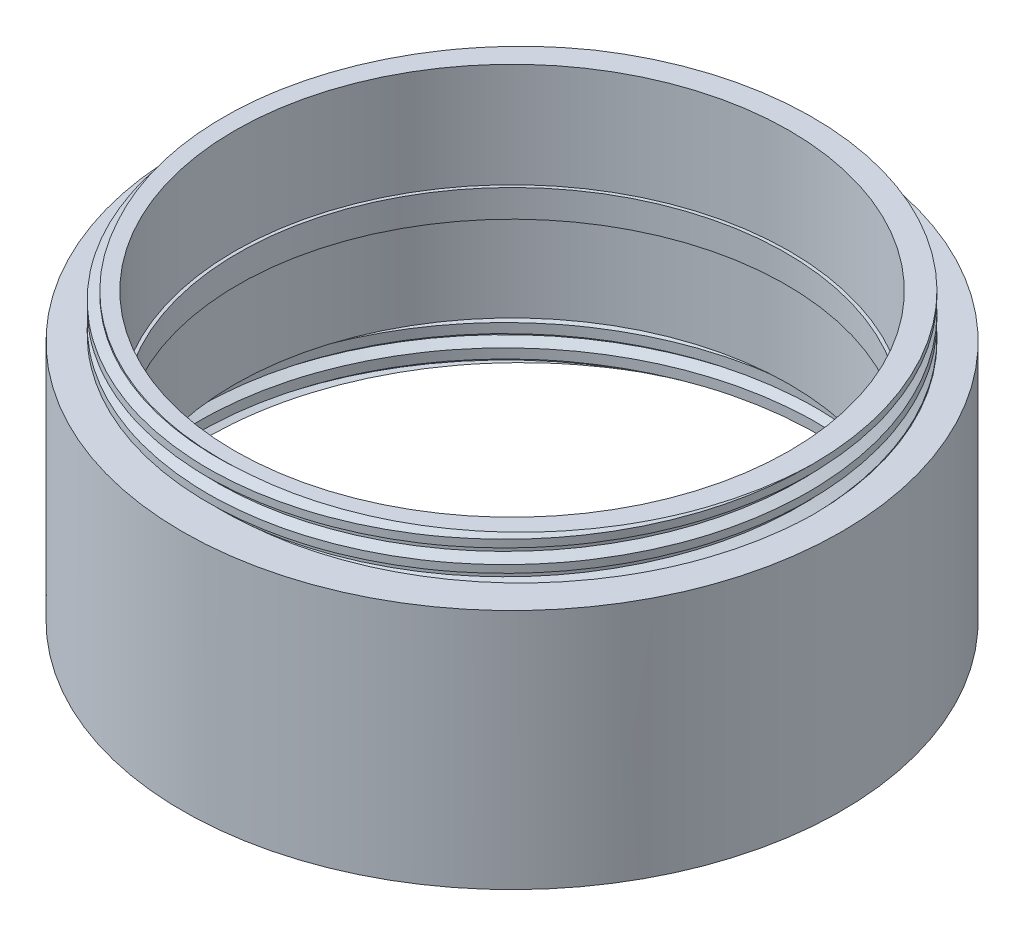
SolidWorks part; units mm, degrees
ref_plane "Front Plane" through (0, 0, 0) normal (0, 0, 1) x (1, 0, 0)
ref_plane "Top Plane" through (0, 0, 0) normal (0, 1, 0) x (1, 0, 0)
ref_plane "Right Plane" through (0, 0, 0) normal (1, 0, 0) x (0, 0, -1)
sketch "Sketch1" plane through (0, 0, 0) normal (0, 1, 0) x (1, 0, 0)
  circle A0 centre (0, 0) radius 30
  dimension "D1" = 60
extrude "Boss-Extrude1" add sketch "Sketch1" along normal blind 15
sketch "Sketch2" plane through (0, 15, 0) normal (0, 1, 0) x (1, 0, 0)
  circle A0 centre (0, 0) radius 25.25
  circle A1 centre (0, 0) radius 30
  circle A2 centre (0, 0) radius 30
  circle A3 centre (0, 0) radius 12.125
  circle M2 centre (0, 0) radius 30
  dimension "D3" = 24.25
  dimension "D1" = 0
  dimension "D2" = 4.75
extrude "Boss-Extrude2" add sketch "Sketch2" along normal blind 15 contours A0 M2 | A3
ref_plane "Plane1" through (0, 24.5, 0) normal (0, 1, 0) x (1, 0, 0)
sketch "Sketch3" [suppressed] plane through (0, 11.5, 0) normal (0, 1, 0) x (1, 0, 0)
  circle A0 centre (0, 0) radius 22.85 construction
  circle A1 centre (0, 0) radius 22.85
  circle A2 centre (0, 0) radius 22.35
  circle A5 centre (0, 0) radius 12.625
  circle A6 centre (0, 0) radius 12.625
  circle A7 centre (0, 0) radius 12.125
  circle A8 centre (0, 0) radius 12.125
  dimension "D1" = 0.5
  dimension "D2" = 0.5
  dimension "D3" = 0
sketch "Sketch4" plane through (0, 15, 0) normal (0, 1, 0) x (1, 0, 0)
  line L0 (0, 0) -> (25.2167, 0) construction
  line L2 (12.125, -2.5) -> (21.125, -2.5)
  line L3 (12.125, -2.5) -> (12.125, 2.5)
  line L4 (12.125, 2.5) -> (21.125, 2.5)
  line L5 (21.125, -2.5) -> (21.125, 2.5)
  line L6 (12.125, -2.5) -> (21.125, 2.5) construction
  line L7 (12.125, 2.5) -> (21.125, -2.5) construction
  circle A0 centre (0, 0) radius 12.125 construction
  point P3 (16.625, 0)
  dimension "D1" = 9
  dimension "D2" = 5
extrude "Cut-Extrude1" cut sketch "Sketch4" against normal through all
sketch "Sketch11" plane through (0, 30, 0) normal (0, 1, 0) x (1, 0, 0)
  circle A0 centre (0, 0) radius 27.35
  circle A1 centre (0, 0) radius 30
  circle A2 centre (0, 0) radius 30
  dimension "D1" = 0
  dimension "D2" = 2.65
extrude "Cut-Extrude2" cut sketch "Sketch11" against normal blind 5
thread "Thread3" pitch 1.5 start angle 0, offset 0, length 7, pitch 2, diameter 54.7
ref_plane "Plane4" through (-27.35, 30, 0) normal (0, 0, -1) x (-1, 0, 0)
sketch "Thread Profile3" plane through (-27.35, 30, 0) normal (0, 0, -1) x (-1, 0, 0)
  line L0 (0, 0) -> (0, 1.5) construction
  line L11 (0, 0) -> (0, 1.3125)
  line L12 (0, 1.3125) -> (-0.8119, 0.8437)
  line L13 (-0.8119, 0.8437) -> (-0.8119, 0.4687)
  line L15 (-0.8119, 0.4687) -> (0, 0)
  line L17 (-0.8119, 0.6562) -> (0, 0.6562) construction
  point P2 (0, 0)
  dimension "Pitch" = 1.5
  dimension "Profile_Angle" = 60
  dimension "Profile_Land" = 0.375
  dimension "Profile_Height" = 0.8119
sketch "Sketch14" plane through (0, 0, 0) normal (0, -1, 0) x (1, 0, 0)
  circle A1 centre (0, 0) radius 30
  circle A2 centre (0, 0) radius 30
  dimension "D1" = 0
extrude "Cut-Extrude3" cut sketch "Sketch14" against normal blind 2
ref_plane "Plane5" through (0, 16, 0) normal (0, 1, 0) x (1, 0, 0)
sketch "Sketch16" plane through (0, 2, 0) normal (0, -1, 0) x (1, 0, 0)
  circle A1 centre (0, 0) radius 30 construction
  circle A2 centre (0, 0) radius 30
extrude "Cut-Extrude5" cut sketch "Sketch16" against normal blind 1
sketch "Sketch17" plane through (0, 30, 0) normal (0, 1, 0) x (1, 0, 0)
  circle A1 centre (0, 0) radius 30
  circle A2 centre (0, 0) radius 30
  dimension "D1" = 0
extrude "Cut-Extrude6" cut sketch "Sketch17" against normal blind 1
sketch "Sketch18" plane through (0, 25, 0) normal (0, 1, 0) x (1, 0, 0)
  line L4 (12.125, -2.5) -> (21.125, -2.5)
  line L5 (12.125, -2.5) -> (21.125, -2.5)
  line L6 (21.125, -2.5) -> (21.125, 2.5)
  line L7 (21.125, -2.5) -> (21.125, 2.5)
  line L8 (21.125, 2.5) -> (12.125, 2.5)
  line L9 (21.125, 2.5) -> (12.125, 2.5)
  line L10 (12.125, 2.5) -> (12.125, -2.5)
  line L11 (12.125, 2.5) -> (12.125, -2.5)
  circle A2 centre (0, 0) radius 30
  circle A3 centre (0, 0) radius 30
  dimension "D1" = 0
  dimension "D2" = 0
extrude "Boss-Extrude5" add sketch "Sketch18" against normal blind 3
sketch "Sketch19" plane through (0, 3, 0) normal (0, -1, 0) x (1, 0, 0)
  circle A0 centre (0, 0) radius 28.1
  circle A1 centre (0, 0) radius 25.25 construction
  circle A2 centre (0, 0) radius 25.25
  dimension "D1" = 2.85
extrude "Cut-Extrude7" cut sketch "Sketch19" against normal blind 6
thread "Thread4" pitch 1.5 profile "Thread Profile4" start angle 0, offset 0, length 6, pitch 2, diameter 56.2
ref_plane "Plane6" through (28.1, 3, 0) normal (0, 0, -1) x (1, 0, 0)
sketch "Thread Profile4" plane through (28.1, 3, 0) normal (0, 0, -1) x (1, 0, 0)
  line L0 (0, 0) -> (0, 1.5) construction
  line L1 (0, 0) -> (0.8119, 0.4687)
  line L2 (0.8119, 0.4687) -> (0.8119, 0.6562)
  line L3 (0.8119, 0.6562) -> (0, 1.125)
  line L4 (0.8119, 0.5625) -> (0, 0.5625) construction
  line L11 (0, 0) -> (0, 1.125)
  point P2 (0, 0)
  dimension "Pitch" = 1.5
  dimension "Profile_Angle" = 60
  dimension "Profile_Land" = 0.1875
  dimension "Profile_Height" = 0.8119
sketch "Sketch23" plane through (0, 29, 0) normal (0, 1, 0) x (1, 0, 0)
  circle A0 centre (0, 0) radius 22.7625
  arc A3 (-23.4296, -12.463) -> (2.5627, -26.4141) centre (0, 0) ccw
  arc A4 (27.35, 0) -> (-15.2092, 22.7311) centre (0, 0) ccw
  arc A5 (-23.4296, -12.463) -> (2.5627, -26.4141) centre (0, 0) ccw
  arc A6 (27.35, 0) -> (-15.2092, 22.7311) centre (0, 0) ccw
  spline S2 degree 3 poles (2767.6646, 1112.6236) (-172.058, 167.5265) (-56.3831, -36.6307) (5.8469, -25.97) (6.6511, -25.7929) (9.0301, -25.1524) (10.5724, -24.581) (12.8163, -23.5038) (13.5452, -23.1114) (14.9651, -22.2599) (15.6574, -21.8) (16.9927, -20.8205) (17.6368, -20.3007) (18.8775, -19.2005) (19.4718, -18.6221) (20.6034, -17.414) (21.1426, -16.7822) (22.1585, -15.4733) (22.6354, -14.7968) (23.5275, -13.4004) (23.9421, -12.6808) (24.7021, -11.2103) (25.0489, -10.4567) (25.6725, -8.9204) (25.9483, -8.14) (26.4284, -6.555) (26.6327, -5.7495) (42.4515, 71.257) (-269.1747, 220.5054) (-1332.7255, -2650.445) knots -4.643249 -4.643249 -4.643249 -4.643249 0.0625 0.0625 0.125 0.125 0.25 0.25 0.3125 0.3125 0.375 0.375 0.4375 0.4375 0.5 0.5 0.5625 0.5625 0.625 0.625 0.6875 0.6875 0.75 0.75 0.8125 0.8125 0.875 0.875 6.743959 6.743959 6.743959 6.743959 only from (2.5627, -26.4141) to (27.35, 0)
  spline S3 degree 3 poles (-1607.3501, -2497.5941) (304.6406, -115.7102) (40.4189, 69.8268) (-17.8074, 20.6857) (-18.4134, 20.1252) (-19.5743, 18.9497) (-20.1293, 18.3341) (-21.1739, 17.0646) (-21.6656, 16.4089) (-22.5882, 15.0557) (-23.0188, 14.3581) (-23.8177, 12.9201) (-24.1869, 12.1778) (-24.8543, 10.6645) (-25.1534, 9.8915) (-25.678, 8.3264) (-25.904, 7.5331) (-26.2833, 5.9249) (-26.4362, 5.1106) (-26.666, 3.4768) (-26.7434, 2.6553) (-26.8623, 0.1768) (-26.7898, -1.4761) (-26.4503, -3.934) (-26.2995, -4.7452) (-25.9229, -6.3517) (-25.6965, -7.1486) (0.9085, -86.5372) (393.7209, -39.0157) (-23.1067, 2959.8154) knots -5.636085 -5.636085 -5.636085 -5.636085 0.0625 0.0625 0.125 0.125 0.1875 0.1875 0.25 0.25 0.3125 0.3125 0.375 0.375 0.4375 0.4375 0.5 0.5 0.5625 0.5625 0.625 0.625 0.75 0.75 0.8125 0.8125 0.875 0.875 7.14206 7.14206 7.14206 7.14206 only from (-15.2092, 22.7311) to (-23.4296, -12.463)
  spline S4 degree 3 poles (2.5627, -26.4141) (3.3903, -26.3513) (4.2155, -26.2494) (5.8469, -25.97) (6.6511, -25.7929) (9.0301, -25.1524) (10.5724, -24.581) (12.8163, -23.5038) (13.5452, -23.1114) (14.9651, -22.2599) (15.6574, -21.8) (16.9927, -20.8205) (17.6368, -20.3007) (18.8775, -19.2005) (19.4718, -18.6221) (20.6034, -17.414) (21.1426, -16.7822) (22.1585, -15.4733) (22.6354, -14.7968) (23.5275, -13.4004) (23.9421, -12.6808) (24.7021, -11.2103) (25.0489, -10.4567) (25.6725, -8.9204) (25.9483, -8.14) (26.4284, -6.555) (26.6327, -5.7495) (27.1328, -3.3152) (27.3177, -1.6592) (27.35, 0) knots 0 0 0 0 0.0625 0.0625 0.125 0.125 0.25 0.25 0.3125 0.3125 0.375 0.375 0.4375 0.4375 0.5 0.5 0.5625 0.5625 0.625 0.625 0.6875 0.6875 0.75 0.75 0.8125 0.8125 0.875 0.875 1 1 1 1
  spline S5 degree 3 poles (-15.2092, 22.7311) (-15.8875, 22.2569) (-16.544, 21.7519) (-17.8074, 20.6857) (-18.4134, 20.1252) (-19.5743, 18.9497) (-20.1293, 18.3341) (-21.1739, 17.0646) (-21.6656, 16.4089) (-22.5882, 15.0557) (-23.0188, 14.3581) (-23.8177, 12.9201) (-24.1869, 12.1778) (-24.8543, 10.6645) (-25.1534, 9.8915) (-25.678, 8.3264) (-25.904, 7.5331) (-26.2833, 5.9249) (-26.4362, 5.1106) (-26.666, 3.4768) (-26.7434, 2.6553) (-26.8623, 0.1768) (-26.7898, -1.4761) (-26.4503, -3.934) (-26.2995, -4.7452) (-25.9229, -6.3517) (-25.6965, -7.1486) (-24.9084, -9.5003) (-24.2372, -11.018) (-23.4296, -12.463) knots 0 0 0 0 0.0625 0.0625 0.125 0.125 0.1875 0.1875 0.25 0.25 0.3125 0.3125 0.375 0.375 0.4375 0.4375 0.5 0.5 0.5625 0.5625 0.625 0.625 0.75 0.75 0.8125 0.8125 0.875 0.875 1 1 1 1
  dimension "D1" = 45.525
  dimension "D2" = 0
ref_plane "Plane7" through (0, 24.5, 0) normal (0, 1, 0) x (1, 0, 0)
sketch "Sketch25" plane through (0, 3, 0) normal (0, -1, 0) x (1, 0, 0)
  circle A1 centre (0, 0) radius 25.25
  circle A2 centre (0, 0) radius 25.25
  dimension "D1" = 0
extrude "Cut-Extrude8" cut sketch "Sketch25" against normal through all
ref_plane "Plane8" through (0, 19.5, 0) normal (0, -1, 0) x (-1, 0, 0)
sketch "Sketch26" plane through (0, 19.5, 0) normal (0, -1, 0) x (-1, 0, 0)
  circle A0 centre (0, 0) radius 25.25 construction
  circle A1 centre (0, 0) radius 25.25
  circle A2 centre (0, 0) radius 24.95
  dimension "D1" = 0.3
extrude "Boss-Extrude6" add sketch "Sketch26" along normal blind 2.5
equation "\"dia\"=50"
equation "\"D1@Sketch1\"=\"dia\"+10"
